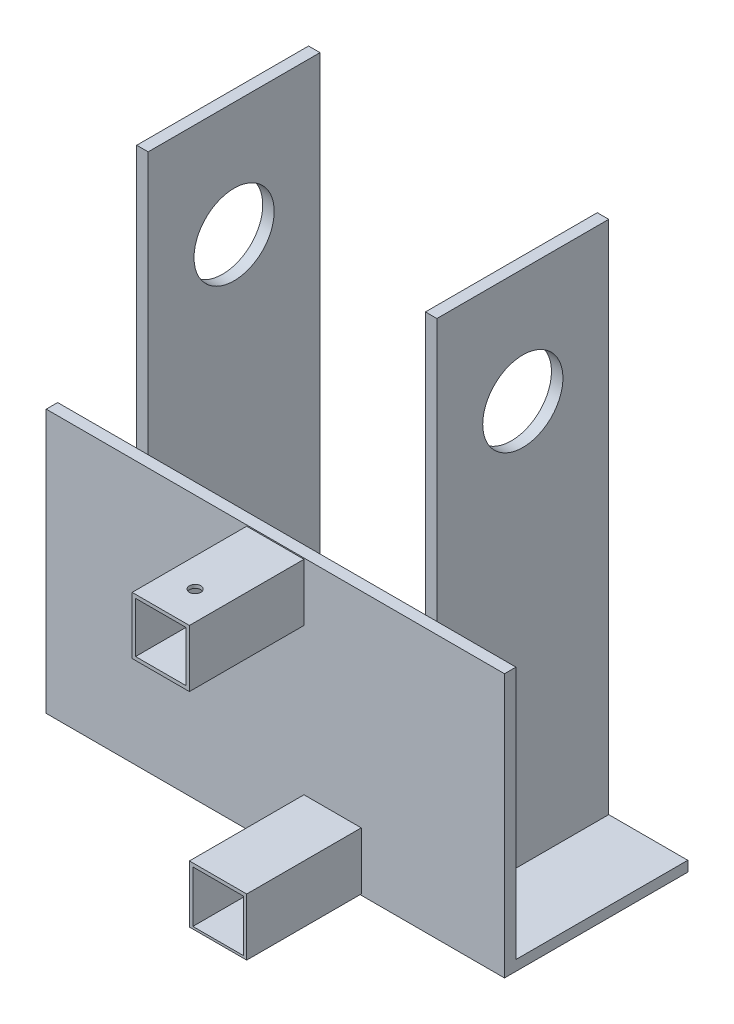
SolidWorks part; units mm, degrees
ref_plane "Plano frontal" through (0, 0, 0) normal (0, 0, 1) x (1, 0, 0)
ref_plane "Plano superior" through (0, 0, 0) normal (0, 1, 0) x (1, 0, 0)
ref_plane "Plano direito" through (0, 0, 0) normal (1, 0, 0) x (0, 0, -1)
sketch "Esboço1" plane through (0, 0, 0) normal (0, 1, 0) x (1, 0, 0)
  line L1 (-200, 75) -> (200, 75)
  line L2 (-200, 75) -> (-200, -75)
  line L3 (-200, -75) -> (200, -75)
  line L4 (200, 75) -> (200, -75)
  line L5 (-200, 75) -> (200, -75) construction
  line L6 (-200, -75) -> (200, 75) construction
  point P0 (0, 0)
  dimension "D1" = 400
  dimension "D2" = 150
extrude "Ressalto-extrusão1" add sketch "Esboço1" along normal blind 9
sketch "Esboço2" plane through (0, 9, 0) normal (0, 1, 0) x (1, 0, 0)
  line L0 (-126, 0) -> (126, 0) construction
  line L1 (-200, -75) -> (200, -75) construction
  line L2 (-131, 75) -> (-121, 75)
  line L3 (-131, 75) -> (-131, -75)
  line L4 (-131, -75) -> (-121, -75)
  line L5 (-121, 75) -> (-121, -75)
  line L6 (-131, 75) -> (-121, -75) construction
  line L7 (-131, -75) -> (-121, 75) construction
  line L8 (0, 75) -> (0, -75) construction
  line L9 (131, -75) -> (121, 75) construction
  line L10 (131, 75) -> (121, -75) construction
  line L11 (121, 75) -> (121, -75)
  line L12 (131, -75) -> (121, -75)
  line L13 (131, 75) -> (131, -75)
  line L14 (131, 75) -> (121, 75)
  point P4 (0, 0)
  point P14 (0, 0)
  dimension "D1" = 10
  dimension "D2" = 242
  dimension "D3" = 150
extrude "Ressalto-extrusão2" add sketch "Esboço2" along normal blind 450
sketch "Esboço5" plane through (-131, 0, 0) normal (-1, 0, 0) x (0, 0, 1)
  line L0 (-75, 459) -> (75, 459) construction
  circle A0 centre (0, 359) radius 35
  dimension "D2" = 70
  dimension "D1" = 100
extrude "Corte-extrusão1" cut sketch "Esboço5" against normal blind 300
sketch "Esboço6" plane through (0, 0, 0) normal (0, -1, 0) x (1, 0, 0)
  line L0 (-200, -75) -> (-200, 75) construction
  line L1 (200, 85) -> (-200, 85)
  line L2 (200, 85) -> (200, 75)
  line L3 (200, 75) -> (-200, 75)
  line L4 (-200, 85) -> (-200, 75)
  line L5 (200, 85) -> (-200, 75) construction
  line L6 (200, 75) -> (-200, 85) construction
  line L7 (200, 75) -> (200, -75) construction
  point P4 (0, 80)
  dimension "D1" = 10
extrude "Ressalto-extrusão4" add sketch "Esboço6" against normal blind 230
ref_plane "Plano1" through (0, 0, 0) normal (-1, 0, 0) x (0, 0, 1)
sketch "Esboço8" plane through (0, 0, 0) normal (-1, 0, 0) x (0, 0, 1)
  line L5 (85, 179) -> (185, 179)
  line L6 (85, 179) -> (85, 229)
  line L7 (85, 230) -> (85, 0) construction
  line L12 (85, 229) -> (185, 229)
  line L13 (185, 179) -> (185, 229)
  line L14 (85, 230) -> (75, 230) construction
  line L15 (85, 179) -> (185, 229) construction
  line L16 (85, 229) -> (185, 179) construction
  point P4 (135, 204)
  dimension "D1" = 50
  dimension "D2" = 100
  dimension "D3" = 1
extrude "Ressalto-extrusão5" add sketch "Esboço8" against normal mid plane 50
sketch "Esboço9" plane through (0, 230, 0) normal (0, 1, 0) x (-1, 0, 0)
  line L0 (0, 75) -> (0, 185) construction
  line L1 (200, 75) -> (-200, 75) construction
  line L2 (-25, 185) -> (25, 185) construction
  circle A0 centre (0, 155) radius 5
  point P12 (0, 75)
  point P17 (0, 185)
  dimension "D1" = 10
  dimension "D2" = 30
extrude "Corte-extrusão3" cut sketch "Esboço9" against normal blind 50
ref_plane "Plano2" through (75, 0, 0) normal (-1, 0, 0) x (0, 0, 1)
sketch "Esboço11" plane through (75, 0, 0) normal (-1, 0, 0) x (0, 0, 1)
  line L1 (85, 51) -> (185, 51)
  line L2 (85, 51) -> (85, 1)
  line L3 (85, 1) -> (185, 1)
  line L4 (185, 51) -> (185, 1)
  line L5 (85, 51) -> (185, 1) construction
  line L6 (85, 1) -> (185, 51) construction
  line L7 (185, 179) -> (185, 229) construction
  line L8 (85, 230) -> (85, 0) construction
  line L12 (-75, 0) -> (85, 0) construction
  point P4 (135, 26)
  dimension "D1" = 1
extrude "Ressalto-extrusão6" add sketch "Esboço11" along normal blind 50
sketch "Esboço12" plane through (25, 0, 0) normal (-1, 0, 0) x (0, 0, 1)
  line L0 (185, 1) -> (185, 51) construction
  circle A0 centre (139.8111, 26) radius 5
  point P4 (185, 26)
  dimension "D1" = 10
extrude "Corte-extrusão4" cut sketch "Esboço12" against normal blind 30
sketch "Esboço13" plane through (0, 0, 185) normal (0, 0, 1) x (1, 0, 0)
  line L0 (-25, 229) -> (-25, 179) construction
  line L1 (72, 3) -> (28, 3)
  line L2 (72, 3) -> (72, 48)
  line L3 (72, 48) -> (28, 48)
  line L4 (28, 3) -> (28, 48)
  line L5 (72, 3) -> (28, 48) construction
  line L6 (72, 48) -> (28, 3) construction
  line L7 (22, 226) -> (-22, 226)
  line L8 (22, 226) -> (22, 182)
  line L9 (22, 182) -> (-22, 182)
  line L10 (-22, 226) -> (-22, 182)
  line L11 (22, 226) -> (-22, 182) construction
  line L12 (22, 182) -> (-22, 226) construction
  line L13 (25, 179) -> (-25, 179) construction
  line L14 (25, 229) -> (-25, 229) construction
  line L15 (25, 179) -> (25, 229) construction
  line L16 (25, 1) -> (25, 51) construction
  line L17 (25, 51) -> (75, 51) construction
  line L18 (-200, 0) -> (200, 0) construction
  line L19 (75, 1) -> (75, 51) construction
  point P0 (50, 25.5)
  point P5 (0, 204)
  dimension "D1" = 3
  dimension "D2" = 3
  dimension "D3" = 3
  dimension "D4" = 3
  dimension "D5" = 3
  dimension "D6" = 3
  dimension "D7" = 3
  dimension "D8" = 3
extrude "Corte-extrusão5" cut sketch "Esboço13" against normal up to surface (100 mm away) up to face at (50, 26, 85)
sketch "Esboço14" plane through (0, 0, 85) normal (0, 0, 1) x (1, 0, 0)
  line L0 (22, 226) -> (-22, 182) construction
  line L1 (72, 48) -> (28, 3) construction
  circle A0 centre (0, 204) radius 5
  circle A1 centre (50, 25.5) radius 5
  dimension "D1" = 10
extrude "Corte-extrusão6" cut sketch "Esboço14" against normal blind 10
